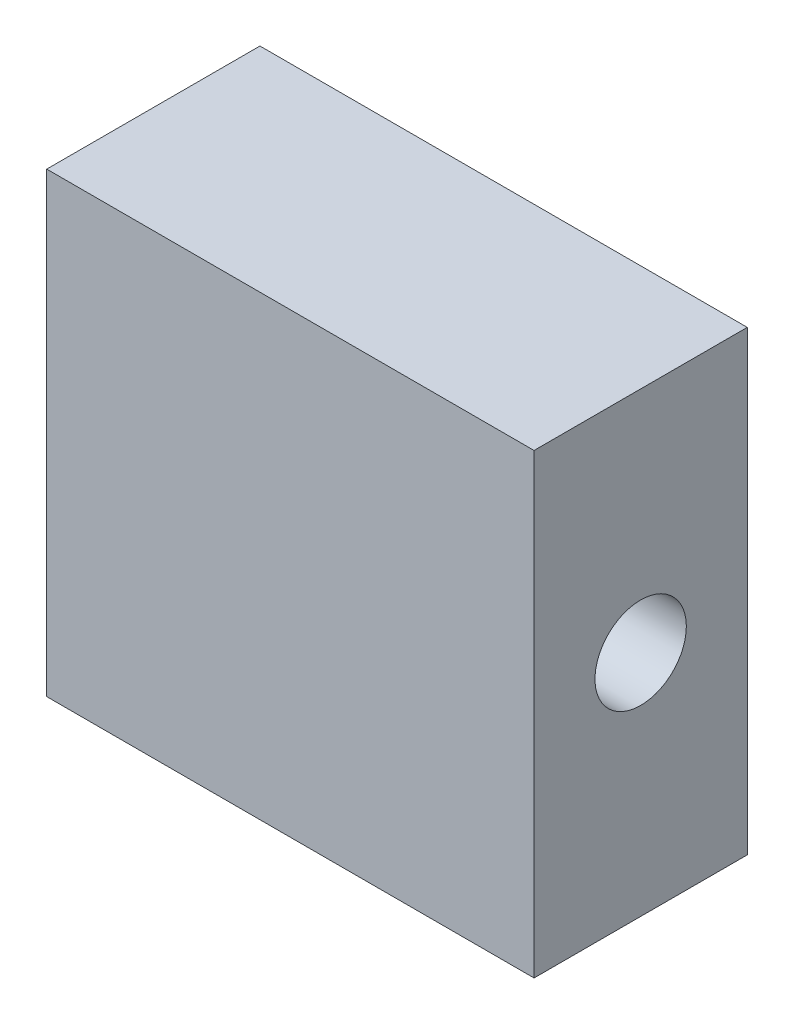
SolidWorks part; units mm, degrees
ref_plane "Front Plane" through (0, 0, 0) normal (0, 0, 1) x (1, 0, 0)
ref_plane "Top Plane" through (0, 0, 0) normal (0, 1, 0) x (1, 0, 0)
ref_plane "Right Plane" through (0, 0, 0) normal (1, 0, 0) x (0, 0, -1)
sketch "Sketch1" plane through (0, 0, 0) normal (0, 0, 1) x (1, 0, 0)
  line L1 (-16, -15) -> (16, -15)
  line L2 (-16, -15) -> (-16, 15)
  line L3 (-16, 15) -> (16, 15)
  line L4 (16, -15) -> (16, 15)
  line L5 (-16, -15) -> (16, 15) construction
  line L6 (-16, 15) -> (16, -15) construction
  point P0 (0, 0)
  point P5 (-10.6667, 10)
  point P6 (-10.6667, -10)
  point P8 (10.6667, -10)
  point P10 (10.6667, 10)
  dimension "D1" = 32
  dimension "D2" = 30
  dimension "D3" = 20
extrude "Boss-Extrude1" add sketch "Sketch1" along normal mid plane 14
hole_wizard "M3x0.5 Tapped Hole1" positions "Sketch2" profile "Sketch4" tap size "M3x0.5" standard "ANSI Metric"
sketch "Sketch2" plane through (0, 0, -7) normal (0, 0, -1) x (-1, 0, 0)
  point P0 (-10.6667, 10)
  point P3 (10.6667, 10)
  point P6 (10.6667, -10)
  point P9 (-10.6667, -10)
sketch "Sketch4" plane through (10.6667, 10, -7) normal (1, 0, 0) x (0, 1, 0)
  line L0 (0, 0) -> (0, 8.2511)
  line L1 (0, 8.2511) -> (1.25, 7.5)
  line L2 (1.25, 7.5) -> (1.25, 0)
  line L5 (1.25, 0) -> (0, 0)
  line L10 (0, 8.2511) -> (-1.25, 7.5) construction
  line L11 (0, -6.35) -> (0, 107.95) construction
  dimension "Tap Drill Dia." = 2.5
  dimension "Tap Drill Depth" = 7.5
  dimension "Drill Angle" = 118
hole_wizard "M6x1.0 Tapped Hole1" positions "Sketch6" profile "Sketch7" tap size "M6x1.0" standard "ANSI Metric" end condition through all
sketch "Sketch6" plane through (16, 0, 0) normal (1, 0, 0) x (0, 0, -1)
  point P0 (0, 0)
sketch "Sketch7" plane through (16, 0, 0) normal (0, 1, 0) x (0, 0, -1)
  line L0 (0, 0) -> (0, 32)
  line L1 (0, 32) -> (3, 32)
  line L2 (3, 32) -> (3, 0)
  line L5 (3, 0) -> (0, 0)
  line L11 (0, -6.35) -> (0, 107.95) construction
  dimension "Thread Major Dia." = 6
  dimension "Thru Tap Drill Depth" = 32
